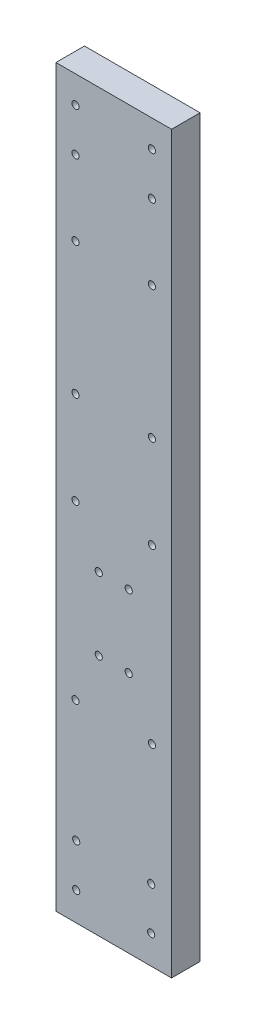
SolidWorks part; units mm, degrees
ref_plane "Front Plane" through (0, 0, 0) normal (0, 0, 1) x (1, 0, 0)
ref_plane "Top Plane" through (0, 0, 0) normal (0, 1, 0) x (1, 0, 0)
ref_plane "Right Plane" through (0, 0, 0) normal (1, 0, 0) x (0, 0, -1)
sketch "Sketch1" plane through (0, 0, 0) normal (0, 0, 1) x (1, 0, 0)
  line L0 (0, 102.96) -> (0, 0)
  line L1 (16.2, 102.96) -> (16.2, 0)
  line L2 (0, 102.96) -> (16.2, 102.96)
  line L3 (0, 0) -> (16.2, 0)
  line L4 (0, 53.64) -> (16.2, 53.64) construction
  line L5 (0, 12.5) -> (16.2, 12.5) construction
  line L6 (0, 24.5) -> (16.2, 24.5) construction
  line L7 (0, 85.165) -> (16.2, 85.165) construction
  line L8 (0, 61.64) -> (16.2, 61.64) construction
  line L10 (0, 91.165) -> (16.2, 91.165) construction
  circle A1 centre (13.45, 51.14) radius 0.5
  circle A2 centre (13.45, 93.165) radius 0.5
  circle A4 centre (2.75, 99.165) radius 0.5
  circle A6 centre (2.75, 51.14) radius 0.5
  circle A7 centre (6, 44.14) radius 0.5
  circle A8 centre (13.45, 27) radius 0.5
  circle A11 centre (6, 34) radius 0.5
  circle A13 centre (2.75, 27) radius 0.5
  circle A16 centre (2.75, 93.165) radius 0.5
  circle A17 centre (13.45, 82.665) radius 0.5
  circle A19 centre (13.45, 64.14) radius 0.5
  circle A20 centre (13.45, 99.165) radius 0.5
  circle A21 centre (10.2, 44.14) radius 0.5
  circle A22 centre (2.75, 82.665) radius 0.5
  circle A23 centre (2.85, 10) radius 0.5
  circle A24 centre (13.35, 10) radius 0.5
  circle A25 centre (13.35, 4) radius 0.5
  circle A26 centre (2.85, 4) radius 0.5
  circle A27 centre (2.75, 64.14) radius 0.5
  circle A30 centre (10.2, 34) radius 0.5
  dimension "D1" = 2.85
  dimension "D2" = 2.85
  dimension "D3" = 2.85
  dimension "D4" = 2.85
  dimension "D5" = 4
  dimension "D6" = 4
  dimension "D7" = 6
  dimension "D8" = 6
  dimension "D9" = 2.5
  dimension "D10" = 12
  dimension "D11" = 29.14
  dimension "D12" = 2.75
  dimension "D13" = 6
  dimension "D14" = 9.5
  dimension "D15" = 2.5
  dimension "D16" = 2.75
  dimension "D17" = 6
  dimension "D18" = 2.5
  dimension "D19" = 9.5
  dimension "D20" = 2.75
  dimension "D21" = 2.75
  dimension "D22" = 6
  dimension "D23" = 6
  dimension "D24" = 9.5
  dimension "D25" = 2.5
  dimension "D26" = 2.5
  dimension "D27" = 9.5
  dimension "D28" = 8
  dimension "D29" = 23.525
  dimension "D30" = 2.75
  dimension "D31" = 2.75
  dimension "D32" = 2.75
  dimension "D33" = 2.75
  dimension "D34" = 2.5
  dimension "D35" = 2.5
  dimension "D36" = 2.5
  dimension "D37" = 2.5
  dimension "D38" = 6
  dimension "D39" = 11.795
  dimension "D40" = 2.75
  dimension "D41" = 2.75
  dimension "D42" = 2.75
  dimension "D43" = 2.75
  dimension "D44" = 2
  dimension "D45" = 8
  dimension "D46" = 2
  dimension "D47" = 8
  dimension "D48" = 16.2
extrude "Boss-Extrude1" add sketch "Sketch1" along normal blind 4
equation "\"D11@Sketch1\"= \"HL@parametersSketch@prostheticParameters.SLDPRT\" * 0.244 - 4 - 12 'Ring PIP Length"
equation "\"D29@Sketch1\"= \"HL@parametersSketch@prostheticParameters.SLDPRT\" * 0.165 - 3 - 4 'Ring MIP Length"
equation "\"D39@Sketch1\"= \"HL@parametersSketch@prostheticParameters.SLDPRT\" * 0.107 - 3 - 5'Ring DIP Length - Fingertip"
equation "\"D48@Sketch1\"= \"fingerWidth@parametersSketch@prostheticParameters.SLDPRT\"'Ring Breadth"
